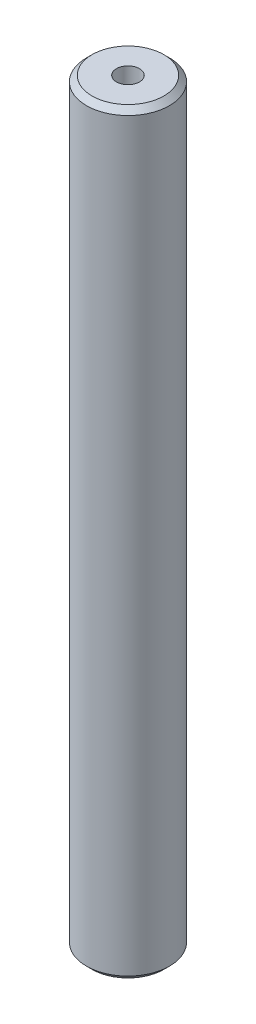
SolidWorks part; units mm, degrees
ref_plane "Front Plane" through (0, 0, 0) normal (0, 0, 1) x (1, 0, 0)
ref_plane "Top Plane" through (0, 0, 0) normal (0, 1, 0) x (1, 0, 0)
ref_plane "Right Plane" through (0, 0, 0) normal (1, 0, 0) x (0, 0, -1)
sketch "Sketch1" plane through (0, 0, 0) normal (0, 1, 0) x (1, 0, 0)
  circle A0 centre (0, 0) radius 17.5
  dimension "SHAFT_OD" = 35
extrude "Boss-Extrude1" add sketch "Sketch1" along normal blind 319.2894
sketch "Sketch2" plane through (0, 0, 0) normal (0, 1, 0) x (1, 0, 0)
  circle A0 centre (0, 0) radius 4.8678
  dimension "BORE_D" = 9.7356
extrude "Cut-Extrude1" cut sketch "Sketch2" along normal through all
chamfer "Chamfer1" distance 2.3597 angle 45 2 edges at (0, 319.2894, 17.5) (0, 0, 17.5)
